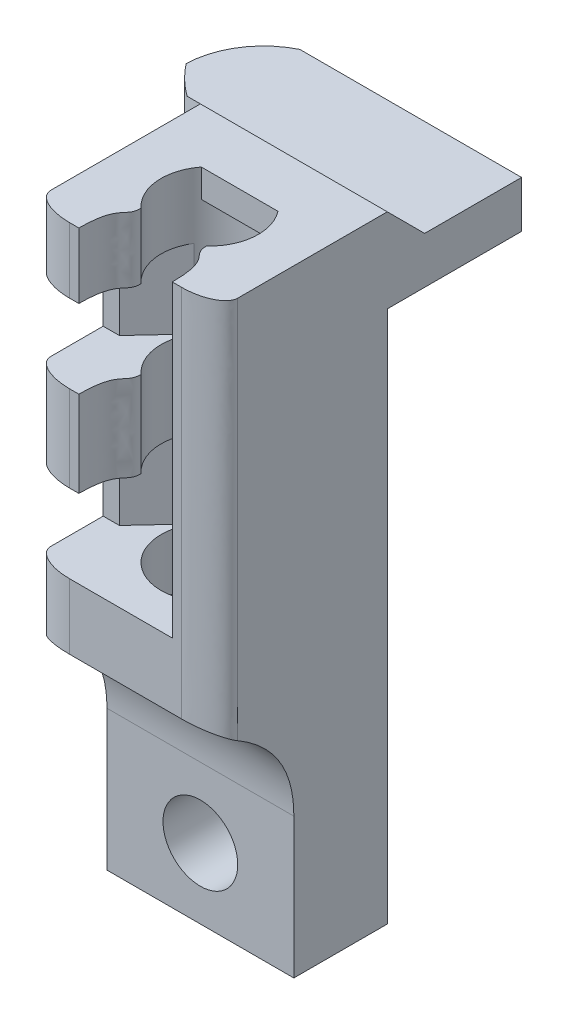
SolidWorks part; units mm, degrees
ref_plane "Front Plane" through (0, 0, 0) normal (0, 0, 1) x (1, 0, 0)
ref_plane "Top Plane" through (0, 0, 0) normal (0, 1, 0) x (1, 0, 0)
ref_plane "Right Plane" through (0, 0, 0) normal (1, 0, 0) x (0, 0, -1)
sketch "Sketch1" plane through (0, 0, 0) normal (1, 0, 0) x (0, 0, -1)
  line L0 (-5, -15) -> (-5, -7.5)
  line L1 (0, 0) -> (0, -15)
  line L2 (0, -15) -> (-5, -15)
  line L3 (0, 0) -> (0, 16)
  line L4 (0, 16) -> (-9, 16)
  line L5 (-9, 16) -> (-9, -2)
  spline S0 degree 2 poles (-5, -7.5) (-4.987, -3.7582) (-9, -2) knots 0 0 0 1 1 1
  dimension "D6" = 18
  dimension "D1" = 16
  dimension "D2" = 15
  dimension "D3" = 5
  dimension "D4" = 9
  dimension "D5" = 7.5
extrude "Boss-Extrude1" add sketch "Sketch1" along normal mid plane 10
sketch "Sketch2" plane through (0, 0, 5) normal (0, 0, 1) x (1, 0, 0)
  line L0 (-5, -15) -> (5, -7.5) construction
  line L1 (-5, -7.5) -> (5, -15) construction
  circle A0 centre (0, -11.25) radius 2
  point P8 (0, -11.25)
  dimension "D1" = 4
extrude "Cut-Extrude1" cut sketch "Sketch2" against normal up to next
sketch "Sketch5" plane through (0, 0, 0) normal (1, 0, 0) x (0, 0, -1)
  line L0 (1.5, 13.5) -> (0, 13.5)
  line L1 (0, 16) -> (-9, 16) construction
  line L2 (0, -15) -> (0, 16) construction
  line L3 (0, -15) -> (0, 16) construction
  line L4 (1.5, 13.5) -> (1.5, 15.2354) construction
  line L5 (1.5, 15.2354) -> (1.1406, 16) construction
  line L6 (1.1406, 16) -> (0, 16) construction
  line L7 (0, 13.5) -> (0, 16)
  spline S0 degree 3 poles (1.5, 13.5) (1.5, 15.2354) (1.1406, 16) (0, 16) knots 0 0 0 0 1 1 1 1
  dimension "D2" = 2.5
  dimension "D1" = 1.5
  dimension "D3" = 1.5
  dimension "D4" = 2.5
extrude "Boss-Extrude2" add sketch "Sketch5" along normal mid plane 10
sketch "Sketch6" plane through (0, 16, 0) normal (0, 1, 0) x (1, 0, 0)
  line L0 (-5, -9) -> (5, 0) construction
  line L1 (5, 0) -> (-5, 0) construction
  line L2 (5, 0) -> (5, 1.5) construction
  line L3 (5, -9) -> (-5, 0) construction
  line L4 (-5, 1.5) -> (-5, 0) construction
  line L5 (-2.0494, -2.9) -> (2.0494, -2.9)
  line L6 (-5, -1.9) -> (5, -1.9) construction
  line L7 (-5, 0) -> (-5, -9) construction
  line L8 (5, 0) -> (5, -9) construction
  circle A0 centre (0, -4.5) radius 2.6
  point P12 (0, -4.5)
  point P23 (0, -1.9)
  dimension "D1" = 5.2
  dimension "D2" = 1.6
extrude "Cut-Extrude4" cut sketch "Sketch6" against normal blind 17.5 contours L5 A0 | L5 A0 region at (0, 16, 2.4926) region at (0, 16, 4.8122)
sketch "Sketch13" plane through (0, 0, 0) normal (0, 1, 0) x (1, 0, 0)
  line L0 (0, 0) -> (0, -9) construction
  line L1 (5, -9) -> (-5, -9) construction
  line L2 (-1.75, -6.4229) -> (-1.75, -7.3) construction
  line L3 (-1.75, -7.3) -> (-2.5, -6.8) construction
  line L4 (-2.5, -9) -> (2.5, -9)
  line L5 (1.75, 0) -> (1.75, -9) construction
  line L6 (5, 0) -> (-5, 0) construction
  line L7 (1.75, -6.4229) -> (1.75, -7.3) construction
  line L8 (1.75, -7.3) -> (2.5, -6.8) construction
  line L9 (2.5, -6.8) -> (2.5, -9) construction
  line L10 (2.5, -9) -> (2.5, -6.8) construction
  line L11 (-2.5, -6.8) -> (-2.5, -9) construction
  circle A1 centre (0, -4.5) radius 2.6 construction
  arc A2 (1.75, -6.4229) -> (-1.75, -6.4229) centre (0, -4.5) cw
  spline S0 degree 3 poles (1.75, -6.4229) (1.75, -7.3) (2.5, -6.8) (2.5, -9) knots 0 0 0 0 1 1 1 1
  spline S1 degree 3 poles (-1.75, -6.4229) (-1.75, -7.3) (-2.5, -6.8) (-2.5, -9) knots 0 0 0 0 1 1 1 1
  point P14 (1.75, -6.4229)
  dimension "D2" = 2.5
  dimension "D3" = 1.75
  dimension "D4" = 2.8
  dimension "D5" = 2.3
  dimension "D6" = 4.5
extrude "Cut-Extrude10" cut sketch "Sketch13" along normal blind 16 from offset 1.5 contours A2 S1 L4 S0 region at (0, 0, 7.9752)
sketch "Sketch15" plane through (0, 0, 9) normal (0, 0, 1) x (1, 0, 0)
  line L0 (0, 0) -> (-5, 0) construction
  line L1 (-5, 16) -> (-5, -2) construction
  line L2 (-5, 5.7) -> (-5, 10.3) construction
  line L3 (-5, 1.5) -> (-1.75, 1.5)
  line L4 (-5, 1.5) -> (-5, 5.7)
  line L5 (-2.5, 1.5) -> (2.5, 1.5) construction
  line L7 (-1.75, 1.5) -> (-1.75, 5.7)
  line L9 (-5, 10.3) -> (-5, 14.5)
  line L15 (-1.75, 16) -> (-1.75, 1.5) construction
  line L16 (-1.75, 5.7) -> (-5, 5.7)
  line L17 (-5, 10.3) -> (-1.75, 10.3)
  line L18 (-1.75, 10.3) -> (-1.75, 14.5)
  line L19 (-1.75, 14.5) -> (-5, 14.5)
  dimension "D2" = 4.2
  dimension "D3" = 4.6
  dimension "D4" = 4.2
extrude "Cut-Extrude11" cut sketch "Sketch15" against normal blind 3.8
chamfer "Chamfer2" distance 4 angle 45 2 edges at (-2.504, 3.6, 5.2) (-2.504, 12.4, 5.2) first distance on face at (-1.4116, 9.6, 5.6161)
sketch "Sketch9" plane through (0, 0, 0) normal (0, 1, 0) x (1, 0, 0)
  line L0 (0, 0) -> (0, 89.861) construction
  line L1 (5, 0) -> (-5, 0) construction
  line L2 (5, 0) -> (5, 1.5) construction
  line L3 (5, 0) -> (-5, 0)
  arc A0 (5, 0) -> (-5, 0) centre (0, 89.861) cw
  dimension "D1" = 90
extrude "Cut-Extrude7" cut sketch "Sketch9" against normal through all and the other way up to surface (13.5 mm away) other way up to face at (0, 13.5, -0.75)
sketch "Sketch12" plane through (0, 13.5, 0) normal (0, -1, 0) x (1, 0, 0)
  line L0 (-5, 0) -> (-5, -0.75)
  line L1 (-5, 0) -> (-5, -1.5) construction
  line L2 (-9.249, -3.4851) -> (-7.4469, -3.2188)
  line L3 (-5, 0) -> (-5, -3.4851) construction
  line L4 (-7.4469, -3.2188) -> (-6.8607, -7.1851)
  line L5 (-5, 0) -> (5, 0)
  line L6 (-5, -3.4851) -> (-9.249, -3.4851) construction
  line L8 (-6.8607, -7.1851) -> (5, -7.1851)
  line L9 (5, -7.1851) -> (5, 0)
  line L15 (-7.2782, -2.9917) -> (-7.4761, -3.0209) construction
  line L16 (-18.1601, -4.5999) -> (-7.2782, -2.9917) construction
  line L17 (-7.4761, -3.0209) -> (-6.8607, -7.1851) construction
  line L18 (-7.249, -3.1895) -> (-9.249, -3.4851) construction
  line L19 (-7.2782, -2.9917) -> (-3.1847, -30.6908) construction
  arc A0 (-9.249, -3.4851) -> (-6.8607, -7.1851) centre (-4.9588, -3.3366) ccw
  arc A1 (-9.249, -3.4851) -> (-5, -0.75) centre (-3.203, -8.2096) cw
  point P14 (-7.4469, -3.2188)
  point P21 (-7.4469, -3.2188)
  point P27 (-7.4469, -3.2188)
  line M4 (-5, 0) -> (-5, -1.5)
  line M5 (-5, -1.5) -> (5, -1.5)
  dimension "D1" = 2
  dimension "D2" = 0.2
  dimension "D3" = 7.1851
  dimension "D4" = 90
  dimension "D5" = 0.2
  dimension "D6" = 90
extrude "Boss-Extrude7" add sketch "Sketch12" against normal up to surface (2.5 mm away) contours A1 L2 L4 M5 M4 | L5 M4 M5 region at (0, 13.5, -0.75) region at (-1.3061, 13.5, -4.2552) up to face at (0, 16, 5.2182)
extrude "Boss-Extrude8" add sketch "Sketch12<4>" along normal blind 2 and the other way up to surface (2.5 mm away) contours L2 A0 L4 region at (-7.9875, 13.5, -4.9075) other way up to face at (-2.1626, 16, 1.8438)
sketch "Sketch12<4>" plane through (0, 13.5, 0) normal (0, -1, 0) x (1, 0, 0) same geometry as "Sketch12"
sketch "Sketch17" plane through (0, 16, 0) normal (0, 1, 0) x (1, 0, 0)
  line L0 (-5, 0.75) -> (-5, -9) construction
  line L1 (5, -9) -> (-5, -9)
  line L2 (5, -9) -> (5, 0)
  line L3 (5, 0) -> (-5, 0)
  line L4 (-5, -9) -> (-5, 0)
extrude "Boss-Extrude10" add sketch "Sketch17" along normal blind 2
extrude "Cut-Extrude12" cut sketch "Sketch13<3>" along normal blind 2 from offset 16
sketch "Sketch13<3>" plane through (0, 0, 0) normal (0, 1, 0) x (1, 0, 0) same geometry as "Sketch13"
extrude "Cut-Extrude13" cut sketch "Sketch6<4>" along normal blind 2 contours L5 A0 region at (0, 16, 4.8122)
sketch "Sketch6<4>" plane through (0, 16, 0) normal (0, 1, 0) x (1, 0, 0) same geometry as "Sketch6"
extrude "Cut-Extrude14" cut sketch "Sketch6<5>" along normal blind 0.5 contours L5 A0 region at (0, 16, 2.4926)
sketch "Sketch6<5>" plane through (0, 16, 0) normal (0, 1, 0) x (1, 0, 0) same geometry as "Sketch6"
fillet "Fillet8" radius 2 1 edges at (5, 8, 9) second distance 1 first distance on face at (0.8333, 5.8333, 9)
fillet "Fillet6" radius 1 3 edges at (-5, -0.25, 9) (-5, 8, 9) (-5, 16.25, 9) second distance 2 first distance on face at (-5, 6.7917, 4.7389)
chamfer "Chamfer3" distance 2 angle 45 1 edges at (0, 16, 0)
